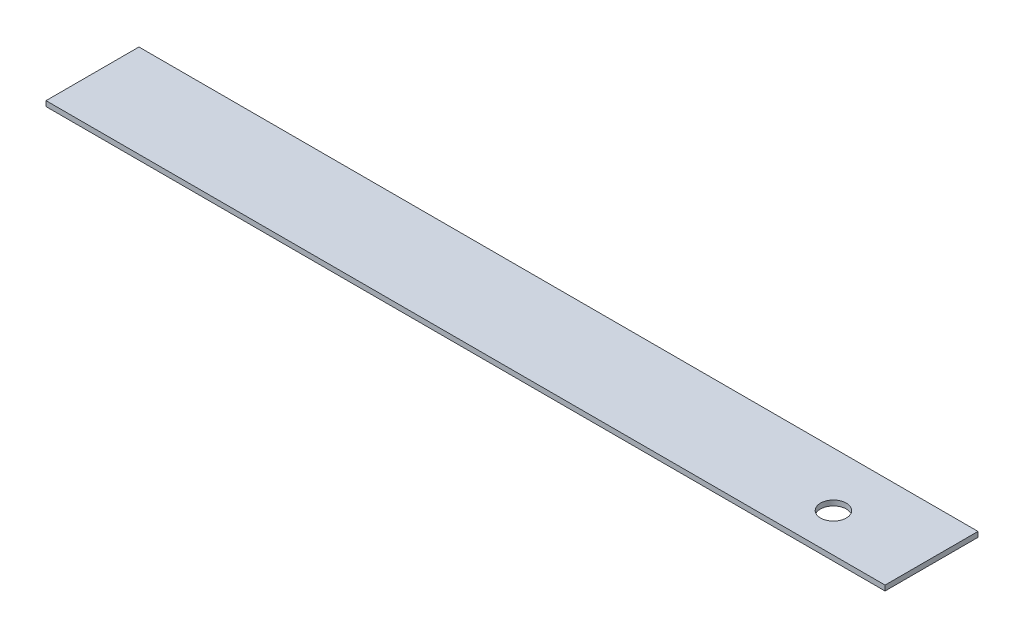
SolidWorks part; units mm, degrees
material "Liga 7079"
ref_plane "Plano frontal" through (0, 0, 0) normal (0, 0, 1) x (1, 0, 0)
ref_plane "Plano superior" through (0, 0, 0) normal (0, 1, 0) x (1, 0, 0)
ref_plane "Plano direito" through (0, 0, 0) normal (1, 0, 0) x (0, 0, -1)
sketch "Esboço1" plane through (0, 0, 0) normal (1, 0, 0) x (0, 0, -1)
  line L1 (-18, 0) -> (18, 0)
  dimension "D1" = 36
sheet metal parameters "Chapa metálica2" thickness 2 parameters "D1"=0.7366, "Espessura"=2
base flange "Flange-base2" sketch "Esboço1" end condition mid plane depth 325 reverse direction no thickness 2 reverse thickness direction no bend radius 0.7366
sketch "Esboço13" plane through (0, -2, 0) normal (0, -1, 0) x (1, 0, 0)
  line L0 (162.5, 18) -> (162.5, -18) construction
  line L2 (162.5, 18) -> (-162.5, 18) construction
  circle A0 centre (127.5, 3) radius 5
  dimension "D1" = 10
  dimension "D2" = 35
  dimension "D3" = 15
extrude "Corte-extrusão4" cut sketch "Esboço13" against normal through all normal cut yes
flat pattern "Padrão-Plano2" [suppressed]
sketch "Curva-Linhas2" plane through (0, 0, 0) normal (0, 1, 0) x (-1, 0, 0)
